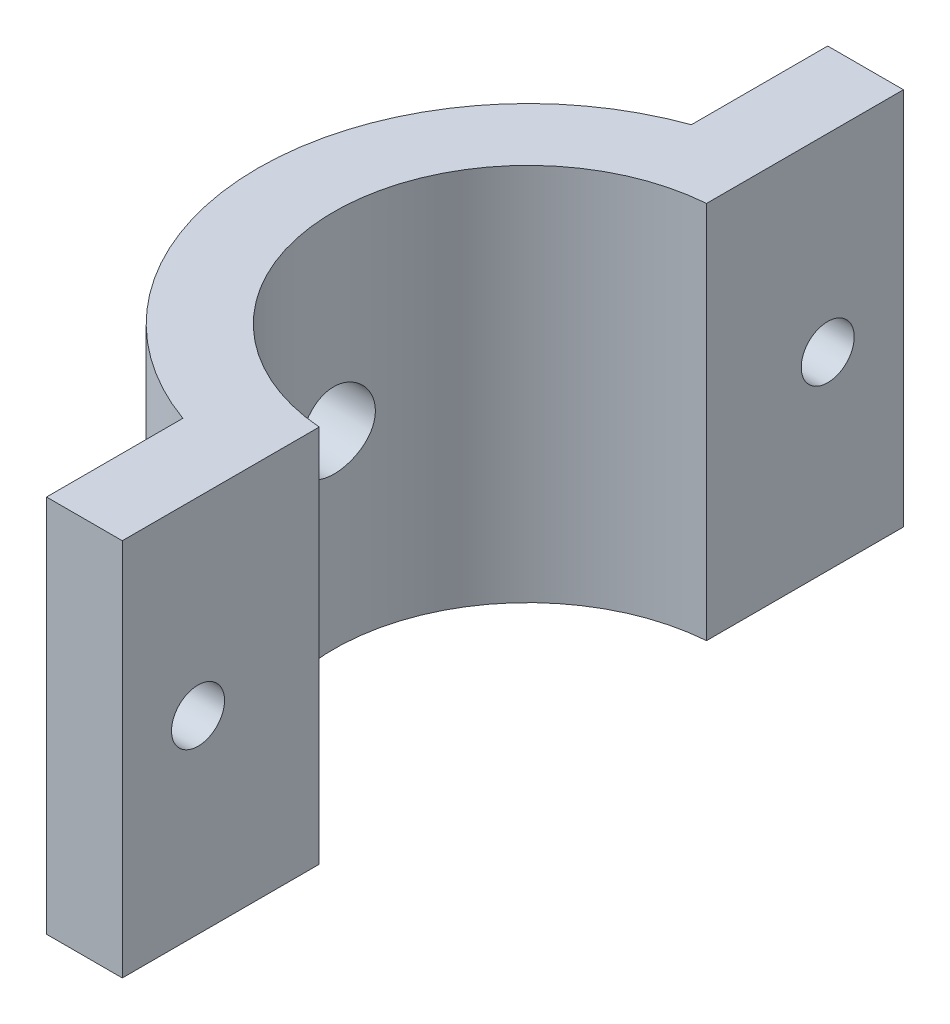
SolidWorks part; units mm, degrees
ref_plane "Front Plane" through (0, 0, 0) normal (0, 0, 1) x (1, 0, 0)
ref_plane "Top Plane" through (0, 0, 0) normal (0, 1, 0) x (1, 0, 0)
ref_plane "Right Plane" through (0, 0, 0) normal (1, 0, 0) x (0, 0, -1)
sketch "Sketch6" plane through (0, 0, 0) normal (0, -1, 0) x (1, 0, 0)
  line L5 (-1, 25.7848) -> (-1, 12.786)
  line L6 (-1, 25.7848) -> (-6, 25.7848)
  line L7 (-6, 25.7848) -> (-6, 16.7848)
  line L8 (-6, -16.7848) -> (-6, -25.7848)
  line L9 (-6, -25.7848) -> (-1, -25.7848)
  line L10 (-1, -25.7848) -> (-1, -12.786)
  line L11 (-12.825, 0) -> (-17.825, 0) construction
  arc A0 (-1, 12.786) -> (-1, -12.786) centre (0, 0) ccw
  arc A1 (-6, 16.7848) -> (-6, -16.7848) centre (0, 0) ccw
  dimension "D1" = 25.65
  dimension "D2" = 5
  dimension "D3" = 1
  dimension "D4" = 9
extrude "Boss-Extrude4" add sketch "Sketch6" along normal blind 25
sketch "Sketch7" plane through (-1, 0, 0) normal (1, 0, 0) x (0, 0, -1)
  line L0 (-20.7848, -25) -> (-20.7848, 0) construction
  line L3 (0, 0) -> (0, -25) construction
  line L6 (-25.7848, -12.5) -> (25.7848, -12.5) construction
  line L13 (-25.7848, -25) -> (-25.7848, 0) construction
  line L14 (25.7848, -25) -> (25.7848, 0) construction
  line L15 (-12.786, -25) -> (12.786, -25) construction
  circle A1 centre (-20.7848, -12.5) radius 1.75
  circle A2 centre (20.7848, -12.5) radius 1.75
  point P0 (0, 0)
  dimension "D1" = 3.5
  dimension "D2" = 5
extrude "Cut-Extrude1" cut sketch "Sketch7" against normal through all
sketch "Sketch8" plane through (0, 0, 0) normal (1, 0, 0) x (0, 0, -1)
  line L0 (-12.786, -25) -> (-12.786, 0) construction
  line L1 (12.786, -25) -> (12.786, 0) construction
  line L2 (-12.786, -12.5) -> (12.786, -12.5) construction
  circle A0 centre (0, -12.5) radius 5
  point P2 (0, 0)
  dimension "D1" = 10
extrude "Boss-Extrude5" add sketch "Sketch8" against normal blind 5 from offset 15 offset against normal yes
sketch "Sketch9" plane through (-20, 0, 0) normal (-1, 0, 0) x (0, 0, 1)
  circle A0 centre (0, -12.5) radius 2.5
  dimension "D1" = 5
extrude "Cut-Extrude2" cut sketch "Sketch9" against normal through all
